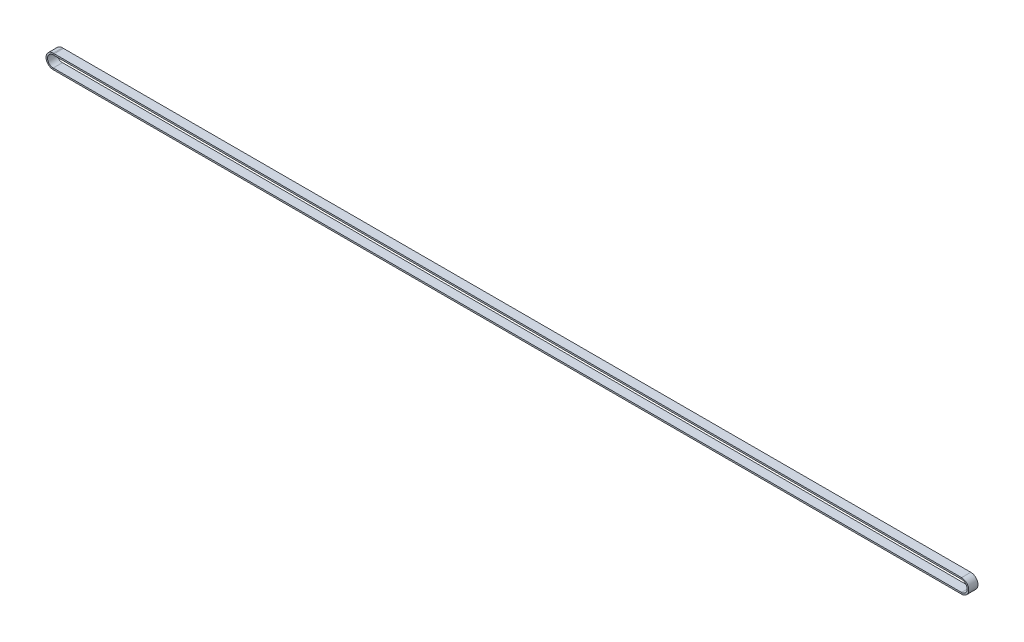
SolidWorks part; units mm, degrees
ref_plane "Front Plane" through (0, 0, 0) normal (0, 0, 1) x (1, 0, 0)
ref_plane "Top Plane" through (0, 0, 0) normal (0, 1, 0) x (1, 0, 0)
ref_plane "Right Plane" through (0, 0, 0) normal (1, 0, 0) x (0, 0, -1)
sketch "Sketch2" plane through (0, 0, 0) normal (0, 0, 1) x (1, 0, 0)
  line L0 (0, 0) -> (1, 0) construction
  line L1 (0, 0) -> (0, 1) construction
  line L2 (-1, -106.8759) -> (883.5204, -106.8759)
  line L3 (883.5204, -120.8759) -> (-1, -120.8759)
  arc A0 (-1, -120.8759) -> (-1, -106.8759) centre (-1, -113.8759) cw
  arc A1 (883.5204, -106.8759) -> (883.5204, -120.8759) centre (883.5204, -113.8759) cw
sketch "Sketch3" plane through (0, 0, 0) normal (1, 0, 0) x (0, 0, -1)
  line L1 (0, -108.3759) -> (-9, -108.3759)
  line L2 (0, -108.3759) -> (0, -106.8759)
  line L3 (0, -106.8759) -> (-9, -106.8759)
  line L4 (-9, -108.3759) -> (-9, -106.8759)
  dimension "D1" = 9
  dimension "D2" = 1.5
sweep "Sweep1" add profiles "Sketch3" path "Sketch2"
